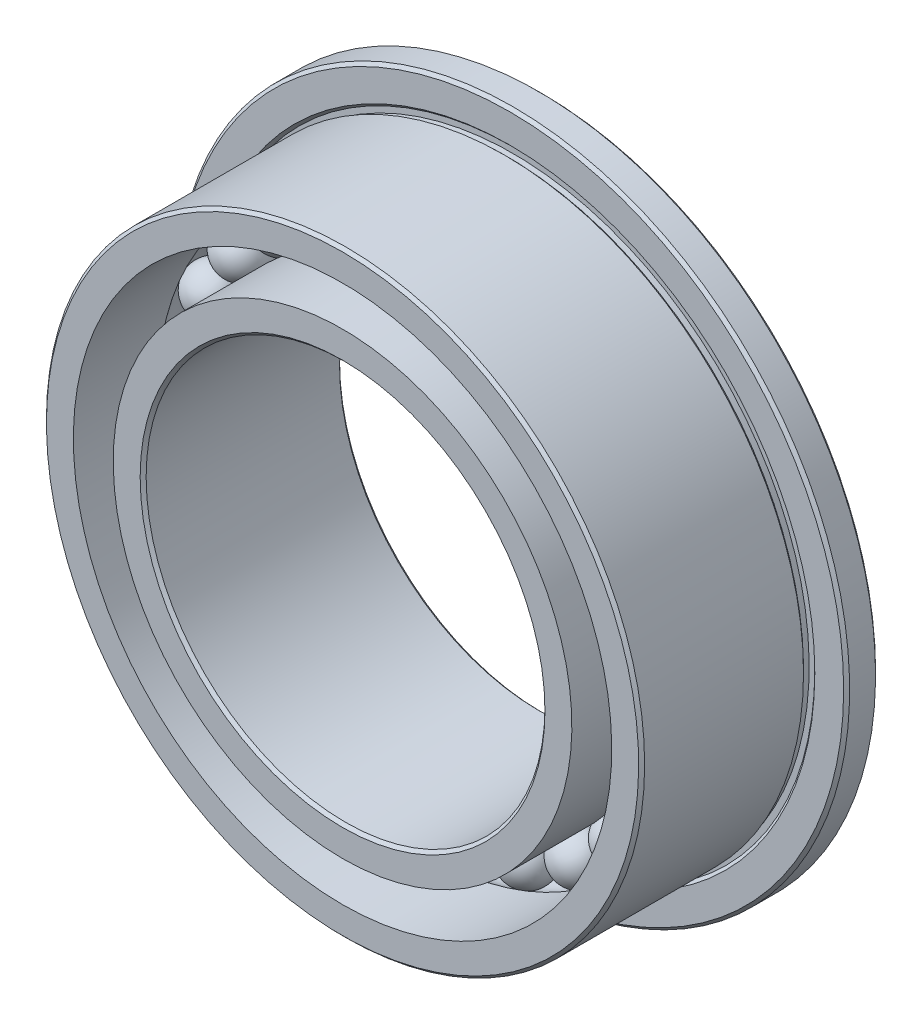
SolidWorks part; units mm, degrees
ref_plane "Front Plane" through (0, 0, 0) normal (0, 0, 1) x (1, 0, 0)
ref_plane "Top Plane" through (0, 0, 0) normal (0, 1, 0) x (1, 0, 0)
ref_plane "Right Plane" through (0, 0, 0) normal (1, 0, 0) x (0, 0, -1)
sketch "Sketch1" plane through (0, 0, 0) normal (1, 0, 0) x (0, 0, -1)
  line L0 (0, 4.7625) -> (0, -4.7625) construction
  line L1 (-1.5875, 4.7625) -> (1.5875, 4.7625) construction
  line L2 (0, 0) -> (1.5875, 0) construction
  line L3 (1.5875, 5.3594) -> (1.5875, -5.3594) construction
  line L4 (1.5875, -5.3594) -> (1.0795, -5.3594) construction
  line L5 (1.5875, 3.175) -> (0, 3.175) construction
  line L6 (1.5875, 3.175) -> (1.5875, -3.175) construction
  dimension "OD" = 9.525
  dimension "Width" = 3.175
  dimension "Flange Dia." = 10.7188
  dimension "Flange Thickness" = 0.508
  dimension "ID" = 6.35
sketch "Sketch2" plane through (0, 0, 0) normal (1, 0, 0) x (0, 0, -1)
  line L0 (1.5875, 5.3594) -> (1.0795, 5.3594)
  line L1 (1.0795, 5.3594) -> (1.0795, 4.8523)
  line L2 (0.9897, 4.7625) -> (-1.5875, 4.7625)
  line L3 (-1.5875, 4.7625) -> (-1.5875, 4.2862)
  line L4 (-1.5875, 4.2862) -> (-0.2381, 4.2862)
  line L5 (1.5875, 5.3594) -> (1.5875, -5.3594) construction
  line L6 (1.5875, 4.2862) -> (1.5875, 5.3594)
  line L7 (1.5875, 3.175) -> (-1.5875, 3.175)
  line L8 (-1.5875, 3.175) -> (-1.5875, 3.6513)
  line L9 (-1.5875, 3.6513) -> (-0.2381, 3.6513)
  line L10 (1.5875, 3.6513) -> (1.5875, 3.175)
  line L11 (0, 4.7625) -> (0, 3.175) construction
  line L12 (-0.3969, 3.9688) -> (0.3969, 3.9688) construction
  line L13 (0.2381, 4.2862) -> (1.5875, 4.2862)
  line L14 (0.2381, 3.6513) -> (1.5875, 3.6513)
  line L15 (1.0795, 4.8523) -> (1.1244, 4.8074)
  line L16 (1.1244, 4.8074) -> (1.1244, 4.7176)
  line L17 (1.1244, 4.7176) -> (1.0346, 4.7176)
  line L18 (1.0346, 4.7176) -> (0.9897, 4.7625)
  line L19 (1.0795, 4.7625) -> (1.1244, 4.7176) construction
  line L20 (1.1244, 4.8074) -> (1.0346, 4.7176) construction
  line L21 (0.9897, 4.7625) -> (1.0795, 4.7625) construction
  line L22 (1.0795, 4.7625) -> (1.0795, 4.8523) construction
  circle A0 centre (0, 3.9688) radius 0.3969 construction
  arc A1 (-0.2381, 4.2862) -> (0.2381, 4.2862) centre (0, 3.9688) cw
  arc A2 (-0.2381, 3.6513) -> (0.2381, 3.6513) centre (0, 3.9688) ccw
  dimension "D1" = 1.5875
  dimension "Ball Dia." = 0.7937
  dimension "D2" = 135
  dimension "D3" = 0.127
  dimension "D4" = 0.635
  dimension "Race Thickness" = 0.4763
revolve "Revolve1" add sketch "Sketch2" angle 360 about L2
fillet "Fillet1" radius 0.0476 3 edges at (0, -5.3594, -1.5875) (0, -5.3594, -1.0795) (0, -4.7625, 1.5875) profile chamfer
sketch "Sketch3" plane through (0, 0, 0) normal (0, 0, 1) x (1, 0, 0)
  line L0 (-3.175, 0) -> (3.175, 0) construction
  line L1 (-4.7625, 0) -> (4.7625, 0) construction
  point P5 (0, 0)
  dimension "ID2" = 6.35
  dimension "OD2" = 9.525
fillet "Fillet2" radius 0.0476 2 edges at (0, -3.175, -1.5875) (0, -3.175, 1.5875) profile chamfer
sketch "Sketch7" plane through (0, 0, 0) normal (0, 0, 1) x (1, 0, 0)
  line L0 (0, 4.3656) -> (0, 3.5719)
  line L1 (0, 5.3594) -> (0, -5.3594) construction
  line L2 (-0.4388, 4.3656) -> (0, 0) construction
  line L3 (0, 0) -> (0.4388, 4.3656) construction
  line L4 (0.4388, 4.3656) -> (-0.4388, 4.3656) construction
  circle A0 centre (0, 3.9688) radius 0.3969 construction
  circle A1 centre (0, 0) radius 4.3656 construction
  circle A2 centre (0, 0) radius 3.5719 construction
  arc A4 (0, 4.3656) -> (0, 3.5719) centre (0, 3.9688) ccw
  dimension "D1" = 11.478
revolve "Revolve3" add sketch "Sketch7" angle 360 about L0
pattern_circular "CirPattern3" count 27 over 360 about axis through (0, 0, 0) along (0, 0, -1) of bodies 107
sketch "Sketch8" [suppressed] plane through (0, 0, 0) normal (1, 0, 0) x (0, 0, -1)
  line L1 (-1.1906, 2.0241) -> (-1.0477, 2.0241)
  line L2 (-1.1906, 2.0241) -> (-1.1906, 2.1431)
  line L3 (-1.1906, 2.1431) -> (-1.0477, 2.1431)
  line L4 (-1.0477, 2.0241) -> (-1.0477, 2.1431)
  line L5 (1.1906, 2.0241) -> (1.0478, 2.0241)
  line L6 (1.1906, 2.0241) -> (1.1906, 2.1431)
  line L7 (1.1906, 2.1431) -> (1.0478, 2.1431)
  line L8 (1.0478, 2.0241) -> (1.0478, 2.1431)
  line L9 (1.1906, 1.5478) -> (1.0478, 1.5478)
  line L10 (1.1906, 1.5478) -> (1.1906, 1.4287)
  line L11 (1.1906, 1.4287) -> (1.0478, 1.4287)
  line L12 (1.0478, 1.5478) -> (1.0478, 1.4287)
  line L13 (-1.1906, 1.5478) -> (-1.0477, 1.5478)
  line L14 (-1.1906, 1.5478) -> (-1.1906, 1.4287)
  line L15 (-1.1906, 1.4287) -> (-1.0477, 1.4287)
  line L16 (-1.0477, 1.5478) -> (-1.0477, 1.4287)
  dimension "D1" = 0.1587
  dimension "D2" = 0.1905
revolve "Cut-Revolve1" [suppressed] cut sketch "Sketch8" angle 360 about L2
sketch "Sketch9" [suppressed] plane through (0, 0, 0) normal (1, 0, 0) x (0, 0, -1)
  line L0 (-1.0477, 2.1431) -> (-1.0477, 1.8657)
  line L1 (-1.0477, 1.8657) -> (-1.1192, 1.7419)
  line L2 (-1.1192, 1.7419) -> (-1.1192, 1.4645)
  line L3 (1.1192, 1.4645) -> (1.1192, 1.4287) construction
  line L4 (1.0478, 2.1431) -> (1.0478, 1.8657)
  line L5 (1.0478, 1.8657) -> (1.1192, 1.7419)
  line L6 (1.1192, 1.7419) -> (1.1192, 1.4645)
  line L7 (1.1906, 1.4287) -> (1.0478, 1.4287) construction
  line L8 (-1.0835, 2.1431) -> (-1.0835, 1.8752)
  line L9 (-1.0835, 1.8752) -> (-1.1549, 1.7515)
  line L10 (-1.1549, 1.7515) -> (-1.1549, 1.4645)
  line L11 (-1.0477, 2.1431) -> (-1.0835, 2.1431)
  line L12 (-1.1192, 1.4645) -> (-1.1549, 1.4645)
  line L13 (1.0835, 2.1431) -> (1.0835, 1.8752)
  line L14 (1.0835, 1.8752) -> (1.1549, 1.7515)
  line L15 (1.1549, 1.7515) -> (1.1549, 1.4645)
  line L16 (1.0478, 2.1431) -> (1.0835, 2.1431)
  line L17 (1.1192, 1.4645) -> (1.1549, 1.4645)
  line L18 (-1.0477, 1.8657) -> (-1.0477, 2.6) construction
  line L19 (1.0478, 1.8657) -> (1.0478, 2.1431) construction
  line L20 (-1.0477, 1.4287) -> (-1.1906, 1.4287) construction
  line L22 (-1.1192, 1.4645) -> (-1.1192, 1.4287) construction
  dimension "D2" = 150
  dimension "D1" = 150
  dimension "D5" = 0.1429
  dimension "D3" = 0.0357
  dimension "D4" = 0.0357
revolve "Revolve4" [suppressed] add sketch "Sketch9" angle 360 about L2
ref_axis "Center Axis 1" through (0, 0, -0.8731) along (0, 0, 1)
ref_plane "Contact Plane 1" through (0, 0, -1.0795) normal (0, 0, 1) x (1, 0, 0)
equation "\"Ball Dia.@Sketch2\"=\"D1@Sketch2\"*.5"
equation "\"D3@Sketch2\"=\"Flange Thickness@Sketch1\"/4"
equation "\"D1@Fillet1\"=\"Race Thickness@Sketch2\"/10"
equation "\"ID2@Sketch3\" = \"ID@Sketch1\""
equation "\"OD2@Sketch3\" = \"OD@Sketch1\""
equation "\"D1@Fillet2\"=\"Race Thickness@Sketch2\"/10"
equation "\"D1@CirPattern3\"=360/\"D1@Sketch7\"-4"
equation "\"D1@Sketch8\"=\"Race Thickness@Sketch2\"/3"
equation "\"D2@Sketch8\"=\"Race Thickness@Sketch2\"/2.5"
equation "\"D3@Sketch9\"=\"D5@Sketch9\"/4"
equation "\"D4@Sketch9\"=\"D5@Sketch9\"/4"
equation "\"D1@Sketch9\"=\"D2@Sketch9\""
equation "\"D4@Sketch2\"=\"D1@Sketch2\"*.4"
